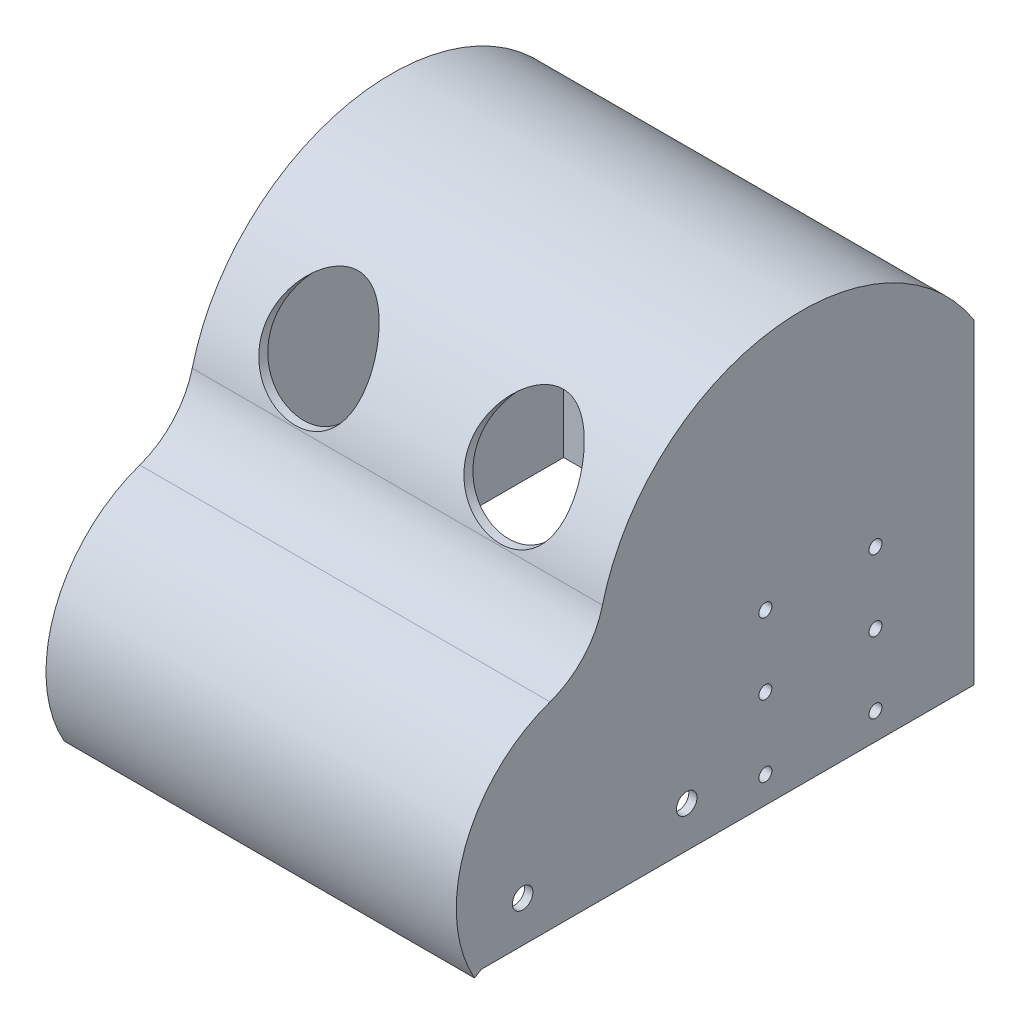
SolidWorks part; units mm, degrees
ref_plane "Front" through (0, 0, 0) normal (0, 0, 1) x (1, 0, 0)
ref_plane "Top" through (0, 0, 0) normal (0, 1, 0) x (1, 0, 0)
ref_plane "Right" through (0, 0, 0) normal (1, 0, 0) x (0, 0, -1)
sketch "Sketch3" plane through (0, 0, 0) normal (1, 0, 0) x (0, 0, -1)
  line L0 (0, 0) -> (152.4, 0)
  line L1 (0, 0) -> (-2.1997, -1.27)
  line L6 (152.4, 0) -> (152.4, 97.9022)
  arc A0 (-2.1997, -1.27) -> (35.5264, 63.5) centre (35.5264, 20.128) cw
  arc A3 (152.4, 97.9022) -> (35.5264, 63.5) centre (99.0264, 63.5) ccw
  dimension "D5" = 127
  dimension "D1" = 152.4
  dimension "D2" = 2.54
  dimension "50" = 150
extrude "Boss-Extrude1" add sketch "Sketch3" along normal blind 127 contours A3 | A3 A0 L1 L0 region at (0, 54.0443, -83.6658)
shell "Shell1" thickness 2.54 removed face at (63.5, 0, -76.2)
sketch "Sketch19" plane through (127, 0, 0) normal (1, 0, 0) x (0, 0, -1)
  line L1 (0, 0) -> (12.7, 0)
  line L2 (0, 0) -> (0, 12.7)
  line L3 (0, 12.7) -> (12.7, 12.7)
  line L4 (12.7, 0) -> (12.7, 12.7)
  circle A0 centre (12.7, 12.7) radius 3.175
  dimension "D3" = 6.35
  dimension "D1" = 12.7
  dimension "D2" = 12.7
extrude "Cut-Extrude5" cut sketch "Sketch19" against normal through all contours L3 A0 L4 | L4 A0 L3 region at (127, 11.3525, -11.3525) region at (127, 13.1492, -13.1492)
sketch "Sketch20" plane through (127, 0, 0) normal (1, 0, 0) x (0, 0, -1)
  line L0 (0, 0) -> (152.4, 0) construction
  line L1 (12.7, 12.7) -> (63.5, 12.7)
  line L2 (12.7, 12.7) -> (12.7, 0)
  line L3 (12.7, 0) -> (63.5, 0)
  line L4 (63.5, 12.7) -> (63.5, 0)
  circle A0 centre (63.5, 12.7) radius 3.175
  dimension "D2" = 6.35
  dimension "D1" = 50.8
extrude "Cut-Extrude7" cut sketch "Sketch20" against normal through all contours A0
fillet "Fillet1" radius 25.4 1 edges at (63.5, 63.5, -35.5264)
sketch "Sketch21" plane through (0, 0, -152.4) normal (0, 0, -1) x (-1, 0, 0)
  line L0 (0, 0) -> (0, 97.9022) construction
  circle A0 centre (-63.5, 57.3841) radius 15.875
  circle A1 centre (-63.5, 57.3841) radius 9.525
  dimension "D2" = 31.75
  dimension "D3" = 19.05
  dimension "D1" = 63.5
extrude "Boss-Extrude2" add sketch "Sketch21" along normal blind 12.7
sketch "Sketch22" plane through (0, 0, -165.1) normal (0, 0, -1) x (-1, 0, 0)
  circle A0 centre (-63.5, 57.3841) radius 27.5
  circle A1 centre (-63.5, 57.3841) radius 14.2875
  dimension "D1" = 55
  dimension "D2" = 28.575
extrude "Boss-Extrude4" add sketch "Sketch22" along normal mid plane 3.175
sketch "Sketch23" plane through (0, 0, -166.6875) normal (0, 0, -1) x (-1, 0, 0)
  circle A0 centre (-63.5, 57.3841) radius 22.5
  circle A1 centre (-63.5, 79.8841) radius 2.5
  circle A2 centre (-41, 57.3841) radius 2.5
  circle A3 centre (-63.5, 34.8841) radius 2.5
  circle A4 centre (-86, 57.3841) radius 2.5
  dimension "D1" = 45
  dimension "D2" = 5
  dimension "D3" = 5
  dimension "D4" = 5
  dimension "D5" = 5
extrude "Cut-Extrude8" cut sketch "Sketch23" against normal blind 3.175 contours A1 | A4 | A3 | A2
sketch "Sketch24" plane through (0, 0, -152.4) normal (0, 0, -1) x (-1, 0, 0)
  line L0 (-63.5, 71.6716) -> (-63.5, 92.6078)
  circle A0 centre (-63.5, 57.3841) radius 14.2875 construction
  circle A1 centre (-63.5, 57.3841) radius 14.2875 construction
  circle A2 centre (-63.5, 85.3241) radius 8.89
  circle A3 centre (-63.5, 57.3841) radius 6.612
  dimension "D1" = 17.78
  dimension "D2" = 27.94
extrude "Cut-Extrude9" cut sketch "Sketch24" against normal blind 12.7 contours A2
sketch "Sketch25" plane through (0, 0, 0) normal (0, 0, 1) x (1, 0, 0)
  line L0 (127, 127) -> (0, 127) construction
  line L1 (0, 127) -> (0, 78.8761) construction
  line L2 (127, 78.8761) -> (127, 127) construction
  circle A0 centre (31.75, 95.25) radius 15.875
  circle A1 centre (95.25, 95.25) radius 15.875
  dimension "D3" = 31.75
  dimension "D4" = 31.75
  dimension "D1" = 31.75
  dimension "D2" = 31.75
  dimension "D5" = 31.75
  dimension "D6" = 31.75
extrude "Cut-Extrude10" cut sketch "Sketch25" against normal blind 63.5
sketch "Sketch26" plane through (0, 0, 0) normal (0, -1, 0) x (1, 0, 0)
  line L2 (90.17, -152.4) -> (36.83, -152.4)
  line L3 (90.17, -152.4) -> (90.17, -114.3)
  line L4 (90.17, -114.3) -> (36.83, -114.3)
  line L5 (36.83, -152.4) -> (36.83, -114.3)
  line L6 (127, -152.4) -> (0, -152.4) construction
  line L7 (0, 0) -> (0, -152.4) construction
  line L10 (44.45, -114.3) -> (82.55, -114.3)
  line L11 (44.45, -114.3) -> (44.45, -152.4)
  line L12 (44.45, -152.4) -> (82.55, -152.4)
  line L13 (82.55, -114.3) -> (82.55, -152.4)
  line M6 (0, -152.4) -> (127, -152.4)
  line M12 (124.46, -149.86) -> (2.54, -149.86)
  dimension "D1" = 38.1
  dimension "D2" = 0
  dimension "D3" = 53.34
  dimension "D4" = 36.83
  dimension "D5" = 38.1
  dimension "D6" = 7.62
extrude "Boss-Extrude5" add sketch "Sketch26" along normal mid plane 63.5 contours L11 L4 L5 M12 | L4 L13 L3 M12 | L13 L3 M12 M6 | L11 L5 M12 M6 region at (86.36, 0, -151.13) region at (86.36, 0, -132.08) region at (40.64, 0, -151.13) region at (40.64, 0, -132.08)
chamfer "Chamfer1" distance 38.1 angle 40 2 edges at (86.36, 31.75, -114.3) (40.64, 31.75, -114.3) first distance on face at (86.36, 31.75, -132.08) first distance on face at (40.64, 31.75, -132.08)
fillet "Fillet2" radius 19.05 4 edges at (86.36, -31.75, -114.3) (86.36, -31.75, -152.4) (40.64, -31.75, -114.3) (40.64, -31.75, -152.4)
sketch "Sketch27" plane through (36.83, 0, 0) normal (-1, 0, 0) x (0, 0, 1)
  circle A1 centre (-133.35, -12.7) radius 4.826
  dimension "D1" = 9.652
extrude "Cut-Extrude11" cut sketch "Sketch27" against normal blind 63.5
sketch "Sketch28" plane through (124.46, 0, 0) normal (-1, 0, 0) x (0, 0, 1)
  line L1 (-152.4, 0) -> (-152.4, 97.9022) construction
  line L2 (-119.46, 60) -> (-124.46, 60)
  line L3 (-119.46, 60) -> (-119.46, 0)
  line L4 (-119.46, 0) -> (-124.46, 0)
  line L5 (0, 0) -> (-152.4, 0) construction
  line L6 (-90.344, 60) -> (-85.344, 60)
  line L7 (-90.344, 60) -> (-90.344, 0)
  line L8 (-90.344, 0) -> (-85.344, 0)
  line L9 (-85.344, 60) -> (-85.344, 0)
  line L10 (-124.46, 60) -> (-124.46, 0)
  dimension "D1" = 5
  dimension "D2" = 27.94
  dimension "D3" = 5
  dimension "D4" = 39.116
  dimension "D5" = 60
extrude "Boss-Extrude6" add sketch "Sketch28" along normal blind 5
sketch "Sketch29" plane through (127, 0, 0) normal (1, 0, 0) x (0, 0, -1)
  line L0 (0, 0) -> (152.4, 0) construction
  line L1 (152.4, 0) -> (152.4, 97.9022) construction
  line L3 (119.38, 63.5) -> (124.46, 63.5)
  line L4 (119.38, 0) -> (124.46, 0)
  line L5 (87.844, 63.5) -> (87.844, 0)
  line L6 (90.344, 0) -> (85.344, 0)
  line L7 (90.344, 0) -> (90.344, 63.5)
  line L8 (90.344, 63.5) -> (85.344, 63.5)
  line L9 (85.344, 0) -> (85.344, 63.5)
  line L10 (119.38, 63.5) -> (119.38, 0)
  line L11 (124.46, 60.564) -> (124.46, 0)
  line L12 (119.38, 0) -> (124.46, 0)
  line L13 (124.46, 63.5) -> (124.46, 0)
  circle A0 centre (87.844, 52.38) radius 2
  circle A1 centre (87.844, 30.38) radius 2
  circle A2 centre (87.844, 8.282) radius 2
  circle A3 centre (121.92, 52.282) radius 2
  circle A4 centre (121.92, 8.282) radius 2
  circle A5 centre (121.92, 30.282) radius 2
  dimension "D6" = 4
  dimension "D7" = 8.282
  dimension "D8" = 4
  dimension "D10" = 4
  dimension "D12" = 4
  dimension "D13" = 4
  dimension "D14" = 39.116
  dimension "D5" = 4
  dimension "D1" = 5
  dimension "D2" = 5.08
  dimension "D3" = 27.94
  dimension "D4" = 63.5
  dimension "D9" = 22
  dimension "D11" = 22.098
  dimension "D15" = 8.282
  dimension "D16" = 22
  dimension "D17" = 22
  dimension "D18" = 63.5
extrude "Cut-Extrude13" cut sketch "Sketch29" against normal up to next contours A0 | A3 | A1 | A5 | A2 | A4
sketch "Sketch30" plane through (82.55, 0, 0) normal (-1, 0, 0) x (0, 0, 1)
  line L0 (-149.86, 0) -> (-149.86, 29.6187) construction
  line L1 (-130.81, -0.2197) -> (-99.6826, -0.2197)
  line L2 (-130.81, -0.2197) -> (-130.81, 24.1507)
  line L3 (-130.81, 24.1507) -> (-99.6826, 24.1507)
  line L4 (-99.6826, -0.2197) -> (-99.6826, 24.1507)
  dimension "D1" = 0
  dimension "D2" = 19.05
extrude "Cut-Extrude14" cut sketch "Sketch30" against normal blind 12.7
sketch "Sketch31" plane through (0, 0, 0) normal (0, -1, 0) x (1, 0, 0)
  line L0 (82.55, -149.86) -> (44.45, -149.86) construction
  line L1 (44.45, -149.86) -> (82.55, -149.86)
  line L2 (44.45, -149.86) -> (44.45, -152.4)
  line L3 (44.45, -152.4) -> (82.55, -152.4)
  line L4 (82.55, -149.86) -> (82.55, -152.4)
  line L5 (82.55, -152.4) -> (44.45, -152.4) construction
extrude "Cut-Extrude15" cut sketch "Sketch31" against normal blind 30.48
